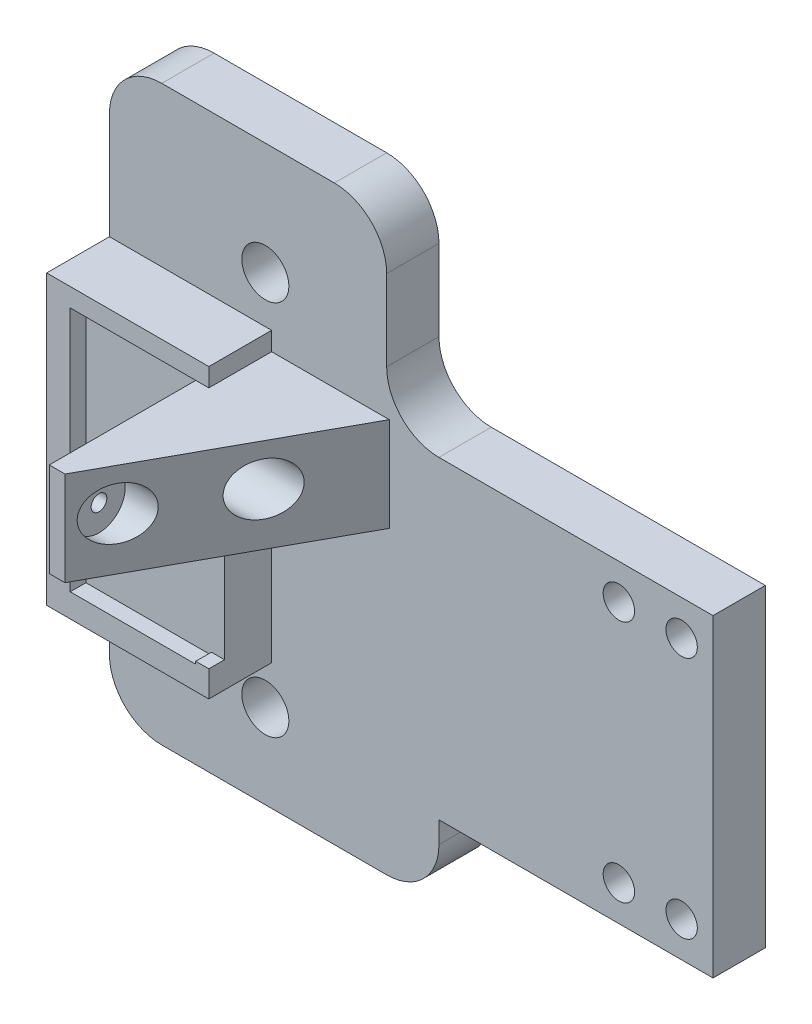
SolidWorks part; units mm, degrees
note: The reader was unsure of these and kept them because the rebuilt part matched: shared geometry of "Sketch1<3>".
ref_plane "Front Plane" through (0, 0, 0) normal (0, 0, 1) x (1, 0, 0)
ref_plane "Top Plane" through (0, 0, 0) normal (0, 1, 0) x (1, 0, 0)
ref_plane "Right Plane" through (0, 0, 0) normal (1, 0, 0) x (0, 0, -1)
sketch "Sketch1" plane through (0, 0, 0) normal (0, 0, 1) x (1, 0, 0)
  line L1 (-6.3, -240.5112) -> (-39.3, -240.5112)
  line L2 (3.7, -250.5112) -> (3.7, -265.9473)
  line L3 (13.7, -335.9473) -> (-39.3, -335.9473)
  line L4 (-49.3, -250.5112) -> (-49.3, -325.9473)
  line L8 (66.093, -275.9473) -> (13.7, -275.9473)
  line L9 (66.093, -275.9473) -> (66.093, -335.9473)
  line L10 (66.093, -335.9473) -> (-49.3, -335.9473)
  line L11 (-49.3, -272.0676) -> (-49.3, -335.9473)
  line L15 (-49.3, -270.9045) -> (-18.3, -270.9045)
  line L16 (-49.3, -270.9045) -> (-49.3, -325.9473)
  line L17 (-49.3, -325.9473) -> (-18.3, -325.9473)
  line L18 (-18.3, -270.9045) -> (-18.3, -325.9473)
  line L21 (-49.3, -335.9473) -> (13.7, -335.9473)
  line L22 (-49.3, -335.9473) -> (-49.3, -340.065)
  line L23 (-39.3, -350.065) -> (3.7, -350.065)
  line L24 (13.7, -335.9473) -> (13.7, -340.065)
  line L25 (-32.8, -274.9473) -> (-22.3, -274.9473) construction
  arc A1 (13.7, -275.9473) -> (3.7, -265.9473) centre (13.7, -265.9473) cw
  arc A2 (3.7, -250.5112) -> (-6.3, -240.5112) centre (-6.3, -250.5112) ccw
  arc A3 (-39.3, -240.5112) -> (-49.3, -250.5112) centre (-39.3, -250.5112) ccw
  arc A4 (13.7, -340.065) -> (3.7, -350.065) centre (3.7, -340.065) cw
  arc A5 (-49.3, -340.065) -> (-39.3, -350.065) centre (-39.3, -340.065) ccw
  point P27 (3.7, -240.5112)
  point P45 (13.7, -350.065)
  dimension "D6" = 10
  dimension "D1" = 4.0428
  dimension "D2" = 60
  dimension "D4" = 33
  dimension "D5" = 31
  dimension "D7" = 115.3929
extrude "Boss-Extrude1" add sketch "Sketch1" along normal blind 10
extrude "Boss-Extrude2" add sketch "Sketch1<3>" along normal up to vertex (19 mm away) contours L16 L15 L18 L17
sketch "Sketch1<3>" plane through (0, 0, 0) normal (0, 0, 1) x (1, 0, 0) same geometry as "Sketch1"
sketch "Sketch2" plane through (0, 0, 19) normal (0, 0, 1) x (1, 0, 0)
  line L0 (-44.3, -320.9473) -> (-44.3, -279.9473) construction
  line L1 (-44.8, -274.4473) -> (-20.8, -274.4473)
  line L2 (-44.8, -274.4473) -> (-44.8, -321.4473)
  line L3 (-44.8, -321.4473) -> (-20.8, -321.4473)
  line L4 (-20.8, -274.4473) -> (-20.8, -321.4473)
  line L5 (-43.3, -274.9473) -> (-32.8, -274.9473) construction
  line L6 (-22.3, -275.9473) -> (-22.3, -319.9473) construction
  line L7 (-22.3, -320.9473) -> (-43.4818, -320.9473) construction
  line L8 (-20.8, -320.9473) -> (-18.3, -320.9473)
  line L9 (-49.3, -270.9045) -> (-18.3, -270.9045)
  line L10 (-49.3, -270.9045) -> (-49.3, -325.9473)
  line L11 (-49.3, -325.9473) -> (-18.3, -325.9473)
  line L12 (-18.3, -270.9045) -> (-18.3, -325.9473)
  line L13 (-20.8, -292.1473) -> (-18.3, -292.1473)
  line M8 (-49.3, -325.9473) -> (-18.3, -325.9473)
  line M9 (-18.3, -325.9473) -> (-18.3, -270.9045)
  line M10 (-18.3, -270.9045) -> (-49.3, -270.9045)
  line M11 (-49.3, -270.9045) -> (-49.3, -325.9473)
  dimension "D1" = 0.5
  dimension "D2" = 0.5
  dimension "D3" = 1.5
  dimension "D4" = 0.5
  dimension "D5" = 28.8
  dimension "D6" = 5
extrude "Boss-Extrude3" add sketch "Sketch2" along normal blind 3 contours L4 L13 L12 L8 L3 L2 L1 M10 M11 M8 M9
sketch "Sketch8" plane through (0, 0, 10) normal (0, 0, 1) x (1, 0, 0)
  line L6 (-20.8, -274.4473) -> (4.2, -274.4473)
  line L7 (-20.8, -274.4473) -> (-20.8, -292.4473)
  line L8 (-20.8, -292.4473) -> (4.2, -292.4473)
  line L9 (4.2, -274.4473) -> (4.2, -292.4473)
  dimension "D1" = 18
  dimension "D2" = 25
extrude "Boss-Extrude4" add sketch "Sketch8" along normal up to surface (40 mm away)
sketch "Sketch9" plane through (0, -292.4473, 0) normal (0, -1, 0) x (1, 0, 0)
  line L0 (-17.8, 50) -> (4.2, 10)
  line L1 (-20.8, 50) -> (4.2, 50) construction
  line L2 (-17.8, 50) -> (4.2, 50)
  line L3 (4.2, 50) -> (4.2, 10)
  dimension "D1" = 3
extrude "Cut-Extrude2" cut sketch "Sketch9" against normal through all
sketch "Sketch11" plane through (-20.8, 0, 0) normal (-1, 0, 0) x (0, 0, 1)
  circle A0 centre (43.5, -282.4473) radius 1.5
  circle A1 centre (25.5, -282.4473) radius 1.5
  dimension "D1" = 3
  dimension "D2" = 3
extrude "Cut-Extrude3" cut sketch "Sketch11" against normal through all
sketch "Sketch12" plane through (3.7, 0, 0) normal (1, 0, 0) x (0, 0, -1)
  circle A0 centre (-43.5, -282.4473) radius 5
  circle A1 centre (-25.5, -282.4473) radius 5
  dimension "D1" = 10
  dimension "D2" = 10
extrude "Cut-Extrude4" cut sketch "Sketch12" against normal up to vertex (21.5 mm away)
sketch "Sketch13" plane through (0, 0, 10) normal (0, 0, 1) x (1, 0, 0)
  line L0 (-49.3, -325.9473) -> (-18.3, -325.9473) construction
  line L2 (-49.3, -325.9473) -> (-49.3, -340.065) construction
  line L3 (-49.3, -250.5112) -> (-49.3, -270.9045) construction
  circle A0 centre (-19.5, -261.9473) radius 4.5
  circle A1 centre (-19.5, -333.9473) radius 4.5
  dimension "D1" = 9
  dimension "D2" = 9
  dimension "D5" = 29.8
  dimension "D3" = 8
  dimension "D4" = 29.8
  dimension "D6" = 72
extrude "Cut-Extrude5" cut sketch "Sketch13" against normal through all
sketch "Sketch14" plane through (0, 0, 10) normal (0, 0, 1) x (1, 0, 0)
  line L1 (60.093, -279.6973) -> (60.093, -285.6973) construction
  line L2 (66.093, -275.9473) -> (13.7, -275.9473) construction
  line L4 (51.093, -288.4473) -> (51.093, -275.9473) construction
  line L7 (66.093, -275.9473) -> (66.093, -335.9473) construction
  line L8 (51.093, -288.4473) -> (66.093, -288.4473) construction
  line L9 (51.093, -289.4473) -> (66.093, -289.4473) construction
  line L10 (51.093, -289.4473) -> (75.093, -289.4473) construction
  line L11 (66.093, -305.9473) -> (44.3743, -305.9473) construction
  circle A0 centre (60.093, -282.6973) radius 3
  circle A1 centre (48.093, -282.6973) radius 3
  circle A2 centre (60.093, -329.1973) radius 3
  circle A3 centre (48.093, -329.1973) radius 3
  point P25 (63.093, -282.6973)
  dimension "D1" = 6
  dimension "D2" = 6
  dimension "D3" = 6.75
  dimension "D4" = 6
  dimension "D5" = 3
extrude "Cut-Extrude6" cut sketch "Sketch14" against normal through all
